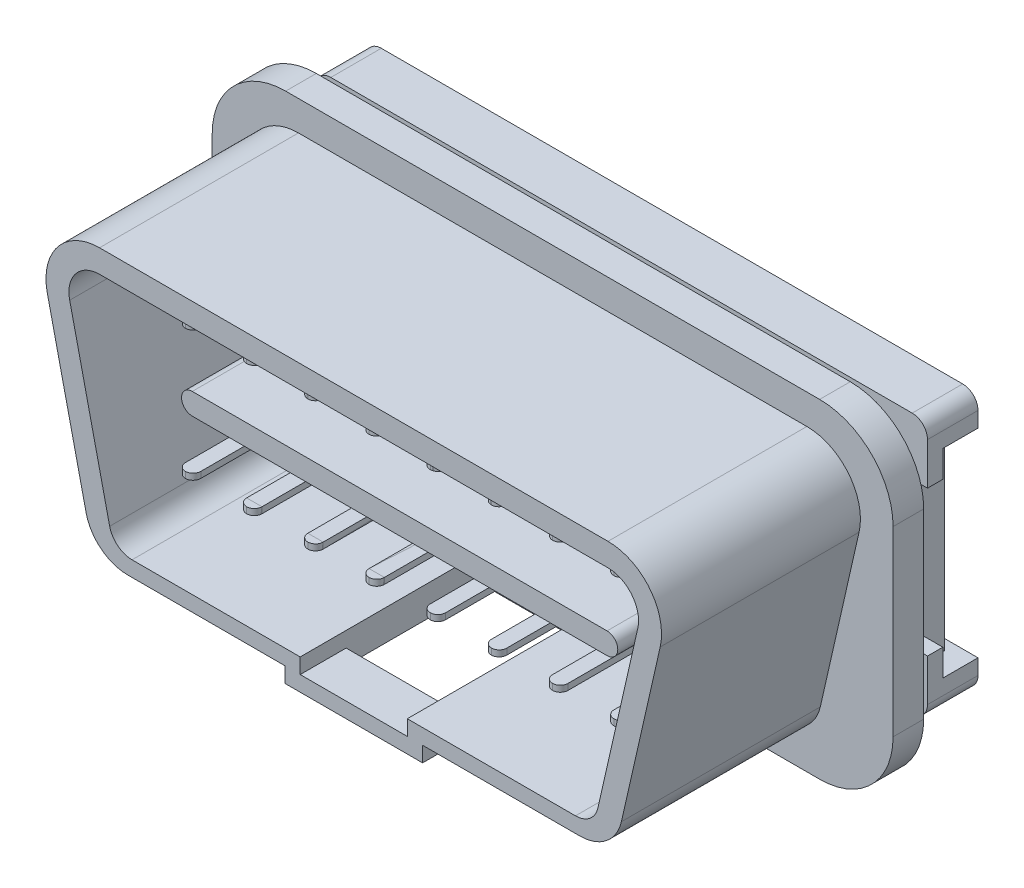
SolidWorks part; units mm, degrees
other "PCB"
other "Body" parameters "D1"=3.3316, "D2"=0.747, "D3"=6.2989, "D4"=6.2989
ref_plane "Front Plane" through (0, 0, 0) normal (0, 0, 1) x (1, 0, 0)
ref_plane "Top Plane" through (0, 0, 0) normal (0, 1, 0) x (1, 0, 0)
ref_plane "Right Plane" through (0, 0, 0) normal (1, 0, 0) x (0, 0, -1)
sketch "Sketch1" plane through (0, 0, 0) normal (0, 0, 1) x (1, 0, 0)
  line L1 (-22.25, -10.75) -> (22.25, -10.75)
  line L2 (-22.25, -10.75) -> (-22.25, 10.75)
  line L3 (-22.25, 10.75) -> (22.25, 10.75)
  line L4 (22.25, -10.75) -> (22.25, 10.75)
  line L5 (-22.25, -10.75) -> (22.25, 10.75) construction
  line L6 (-22.25, 10.75) -> (22.25, -10.75) construction
  point P0 (0, 0)
  dimension "D1" = 44.5
  dimension "D2" = 21.5
extrude "Boss-Extrude1" add sketch "Sketch1" along normal blind 2
sketch "Sketch2" plane through (0, 0, 2) normal (0, 0, 1) x (1, 0, 0)
  line L0 (-16.6153, 8.8) -> (16.6153, 8.8)
  line L1 (20.0283, 4.5243) -> (17.4926, -6.6324)
  line L2 (14.7772, -8.8) -> (-14.7772, -8.8)
  line L3 (-17.4926, -6.6324) -> (-20.0283, 4.5243)
  line L4 (-16.6153, 7.3) -> (16.6153, 7.3)
  line L5 (18.5656, 4.8568) -> (15.9544, -6.6324)
  line L6 (14.4917, -7.8) -> (-14.4917, -7.8)
  line L7 (-15.9544, -6.6324) -> (-18.5656, 4.8568)
  line L8 (0, 7.3) -> (0, 8.8) construction
  line L9 (-17.26, -0.8878) -> (-18.7227, -1.2203) construction
  line L10 (17.26, -0.8878) -> (18.7227, -1.2203) construction
  line L11 (4.4115, 8.8) -> (4.4115, -8.8) construction
  arc A0 (16.6153, 7.3) -> (18.5656, 4.8568) centre (16.6153, 5.3) cw
  arc A1 (-16.6153, 7.3) -> (-18.5656, 4.8568) centre (-16.6153, 5.3) ccw
  arc A2 (16.6153, 8.8) -> (20.0283, 4.5243) centre (16.6153, 5.3) cw
  arc A3 (-16.6153, 8.8) -> (-20.0283, 4.5243) centre (-16.6153, 5.3) ccw
  arc A4 (15.9544, -6.6324) -> (14.4917, -7.8) centre (14.4917, -6.3) cw
  arc A5 (-14.4917, -7.8) -> (-15.9544, -6.6324) centre (-14.4917, -6.3) cw
  arc A6 (17.4926, -6.6324) -> (14.7772, -8.8) centre (14.7772, -6.0153) cw
  arc A7 (-14.7772, -8.8) -> (-17.4926, -6.6324) centre (-14.7772, -6.0153) cw
  point P3 (0, 8.8)
  point P5 (0, -8.8)
  point P7 (-18.7604, -1.0541)
  point P8 (18.7604, -1.0541)
  point P25 (21, 8.8)
  point P28 (-21, 8.8)
  point P29 (4.4115, 0)
  point P36 (17, -8.8)
  point P39 (-17, -8.8)
  dimension "D6" = 2
  dimension "D7" = 1.5
  dimension "D1" = 42
  dimension "D2" = 17.6
  dimension "D3" = 34
  dimension "D4" = 1.5
  dimension "D5" = 1
extrude "Boss-Extrude2" add sketch "Sketch2" along normal blind 13
sketch "Sketch3" plane through (0, 0, 15) normal (0, 0, 1) x (1, 0, 0)
  line L0 (-14.7772, -8.8) -> (14.7772, -8.8) construction
  line L1 (-4.5, -8.8) -> (4.5, -8.8)
  line L2 (-4.5, -8.8) -> (-4.5, -9.8)
  line L3 (-4.5, -9.8) -> (4.5, -9.8)
  line L4 (4.5, -8.8) -> (4.5, -9.8)
  point P6 (0, -8.8)
  point P7 (0, -8.8)
  dimension "D1" = 1
  dimension "D2" = 9
extrude "Boss-Extrude3" add sketch "Sketch3" against normal up to surface (13 mm away) up to face at (0, 0, 2)
sketch "Sketch4" plane through (0, 0, 15) normal (0, 0, 1) x (1, 0, 0)
  line L0 (-14.4917, -7.8) -> (14.4917, -7.8) construction
  line L1 (-3.5, -7.8) -> (3.5, -7.8)
  line L2 (-3.5, -7.8) -> (-3.5, -8.8)
  line L3 (-3.5, -8.8) -> (3.5, -8.8)
  line L4 (3.5, -7.8) -> (3.5, -8.8)
  line L5 (-14.7772, -8.8) -> (-4.5, -8.8) construction
  line L6 (-4.5, -9.8) -> (4.5, -9.8) construction
  line L7 (-3.5, -8.8) -> (-4.5, -8.8) construction
  line L8 (-4.5, -8.8) -> (-4.5, -9.8) construction
  point P8 (0, -7.8)
  point P11 (0, -9.8)
extrude "Cut-Extrude1" cut sketch "Sketch4" against normal up to surface (13 mm away) up to face at (0, -0.5156, 2)
sketch "Sketch5" plane through (0, -8.8, 0) normal (0, 1, 0) x (1, 0, 0)
  line L0 (3.5, -2) -> (3.5, -15) construction
  line L1 (-3.5, -2) -> (3.5, -2)
  line L2 (-3.5, -2) -> (-3.5, -12)
  line L3 (-3.5, -12) -> (3.5, -12)
  line L4 (3.5, -2) -> (3.5, -12)
  dimension "D1" = 10
extrude "Cut-Extrude2" cut sketch "Sketch5" against normal through all
sketch "Sketch6" plane through (0, 0, 2) normal (0, 0, 1) x (1, 0, 0)
  line L0 (-13.555, 0) -> (13.555, 0) construction
  line L1 (-13.555, 0.7) -> (13.555, 0.7)
  line L2 (-13.555, -0.7) -> (13.555, -0.7)
  arc A0 (-13.555, 0.7) -> (-13.555, -0.7) centre (-13.555, 0) ccw
  arc A1 (13.555, -0.7) -> (13.555, 0.7) centre (13.555, 0) ccw
  point P2 (0, 0)
  point P8 (14.255, 0)
  point P9 (-14.255, 0)
  dimension "D1" = 1.4
  dimension "D2" = 28.51
extrude "Boss-Extrude4" add sketch "Sketch6" along normal blind 10
sketch "Sketch7" plane through (0, 0, 0) normal (0, 0, -1) x (-1, 0, 0)
  line L1 (-18, -6.75) -> (18, -6.75)
  line L2 (-18, -6.75) -> (-18, 6.75)
  line L3 (-18, 6.75) -> (18, 6.75)
  line L4 (18, -6.75) -> (18, 6.75)
  line L5 (-18, -6.75) -> (18, 6.75) construction
  line L6 (-18, 6.75) -> (18, -6.75) construction
  point P0 (0, 0)
  dimension "D1" = 36
  dimension "D2" = 13.5
extrude "Boss-Extrude5" add sketch "Sketch7" along normal blind 2.5
sketch "Sketch8" plane through (0, 0, -2.5) normal (0, 0, -1) x (-1, 0, 0)
  line L0 (-18, 0) -> (18, 0) construction
  line L1 (-18, 6.75) -> (-18, -6.75) construction
  line L2 (18, -6.75) -> (18, 6.75) construction
  line L3 (0, 4.75) -> (0, 0) construction
  line L4 (-20, 8.5) -> (20, 8.5)
  line L5 (-20, 8.5) -> (-20, 4.75)
  line L6 (-20, 4.75) -> (20, 4.75)
  line L7 (20, 8.5) -> (20, 4.75)
  line L8 (-20, -8.5) -> (20, -8.5)
  line L9 (-20, -8.5) -> (-20, -4.75)
  line L10 (-20, -4.75) -> (20, -4.75)
  line L11 (20, -8.5) -> (20, -4.75)
  line L12 (0, 0) -> (0, -4.75) construction
  dimension "D1" = 17
  dimension "D2" = 9.5
  dimension "D3" = 40
extrude "Boss-Extrude6" add sketch "Sketch8" along normal blind 1
sketch "Sketch9" plane through (0, 0, -3.5) normal (0, 0, -1) x (-1, 0, 0)
  line L0 (20, 4.75) -> (20, 8.5) construction
  line L1 (-20, 8.5) -> (20, 8.5)
  line L2 (-20, 8.5) -> (-20, 6.5)
  line L3 (-20, 6.5) -> (20, 6.5)
  line L4 (20, 8.5) -> (20, 6.5)
  line L5 (-20, -4.75) -> (-20, -8.5) construction
  line L6 (20, -8.5) -> (-20, -8.5)
  line L7 (20, -8.5) -> (20, -6.5)
  line L8 (20, -6.5) -> (-20, -6.5)
  line L9 (-20, -8.5) -> (-20, -6.5)
  dimension "D1" = 2
extrude "Boss-Extrude7" add sketch "Sketch9" along normal offset from surface (2.3 mm away) 3.3 up to face at (0, 6.1875, -2.5)
sketch "Sketch10" plane through (0, 0, -3.5) normal (0, 0, -1) x (-1, 0, 0)
  line L0 (-20, 6.5) -> (20, 6.5) construction
  line L1 (-18.5, -6.5) -> (18.5, -6.5)
  line L2 (-18.5, -6.5) -> (-18.5, 6.5)
  line L3 (-18.5, 6.5) -> (18.5, 6.5)
  line L4 (18.5, -6.5) -> (18.5, 6.5)
  line L5 (-18.5, -6.5) -> (18.5, 6.5) construction
  line L6 (-18.5, 6.5) -> (18.5, -6.5) construction
  point P0 (0, 0)
  dimension "D1" = 37
extrude "Boss-Extrude8" add sketch "Sketch10" along normal blind 1.6 separate body
sketch "Sketch11" plane through (0, 0, 2) normal (0, 0, 1) x (1, 0, 0)
  line L0 (2, -4.25) -> (2, 4.25) construction
  line L1 (1.5, 4.05) -> (2.5, 4.05)
  line L2 (1.5, 4.05) -> (1.5, 4.45)
  line L3 (1.5, 4.45) -> (2.5, 4.45)
  line L4 (2.5, 4.05) -> (2.5, 4.45)
  line L5 (1.5, 4.05) -> (2.5, 4.45) construction
  line L6 (1.5, 4.45) -> (2.5, 4.05) construction
  line L7 (1.5, -4.45) -> (2.5, -4.45)
  line L8 (1.5, -4.45) -> (1.5, -4.05)
  line L9 (1.5, -4.05) -> (2.5, -4.05)
  line L10 (2.5, -4.45) -> (2.5, -4.05)
  line L11 (1.5, -4.45) -> (2.5, -4.05) construction
  line L12 (1.5, -4.05) -> (2.5, -4.45) construction
  point P0 (2, 4.25)
  point P5 (2, -4.25)
  point P10 (2, 0)
  dimension "D1" = 1
  dimension "D2" = 0.4
  dimension "D3" = 2
  dimension "D4" = 8.5
extrude "Boss-Extrude9" add sketch "Sketch11" along normal blind 10 and the other way offset from surface (8.6 mm away) 1.5 separate body other way up to face at (0, 0, -5.1)
fillet "Fillet1" radius 0.5 2 edges at (1.5, 4.25, 12) (2.5, 4.25, 12)
fillet "Fillet2" radius 0.5 2 edges at (1.5, -4.25, 12) (2.5, -4.25, 12)
pattern_linear "LPattern4" count 4 spacing 4 along (1, 0, 0) count 5 spacing 4 along (-1, 0, 0) of "Fillet2", "Fillet1", "Boss-Extrude9"
fillet "Fillet3" radius 4.8 4 edges at (-22.25, -10.75, 1) (22.25, -10.75, 1) (-22.25, 10.75, 1) (22.25, 10.75, 1)
fillet "Fillet4" radius 1 4 edges at (-20, 8.5, -4.15) (-20, -8.5, -4.15) (20, -8.5, -4.15) (20, 8.5, -4.15)
ref_plane "Plane1" through (0, 0, 0) normal (1, 0, 0) x (0, 0, -1)
ref_plane "Plane2" through (0, 0, 0) normal (0, 1, 0) x (1, 0, 0)
ref_plane "Plane3" through (0, -2.5, 0) normal (0, 1, 0) x (1, 0, 0)
equation "\"D1@Fillet1\"=\"D1@Sketch11\"/2"
equation "\"D1@Fillet2\"=\"D1@Fillet1\""
